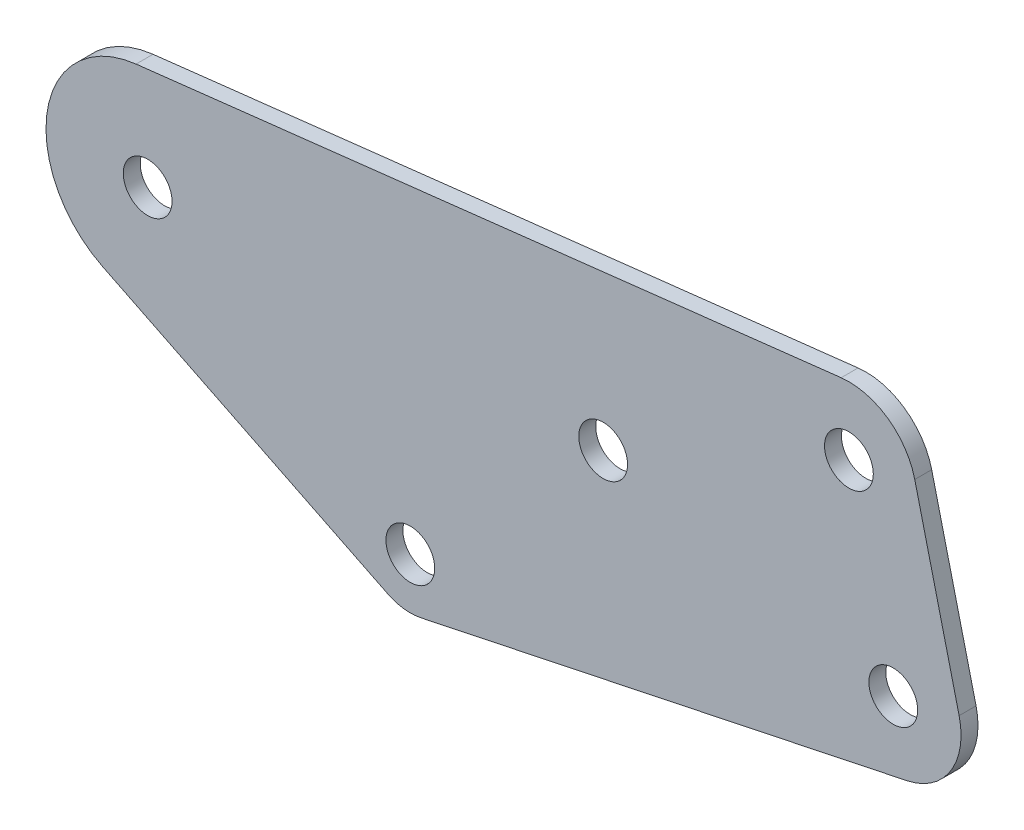
SolidWorks part; units mm, degrees
material "Delrin 2700 NC010, Low Viscosity Acetal Copolymer (SS)"
ref_plane "Front Plane" through (0, 0, 0) normal (0, 0, 1) x (1, 0, 0)
ref_plane "Top Plane" through (0, 0, 0) normal (0, 1, 0) x (1, 0, 0)
ref_plane "Right Plane" through (0, 0, 0) normal (1, 0, 0) x (0, 0, -1)
sketch "Sketch1" plane through (0, 0, 0) normal (0, 0, 1) x (1, 0, 0)
  line L0 (65.6922, 10.7345) -> (42.672, 0) construction
  line L1 (64.9683, 17.0431) -> (-1.0859, 9.4629)
  line L2 (-4.2174, -8.5404) -> (22.4975, -21.7327)
  line L5 (0, 0) -> (42.672, 0) construction
  line L6 (24.6063, -17.4625) -> (24.6062, 0) construction
  line L7 (0, 0) -> (47.7528, 0) construction
  line L8 (25.584, -22.1236) -> (71.1536, -12.5647)
  line L9 (76.0199, -4.8485) -> (71.8621, 12.236)
  circle A0 centre (0, 0) radius 2.286
  circle A1 centre (42.672, 0) radius 2.286
  circle A2 centre (65.6922, 10.7345) radius 2.286
  circle A3 centre (24.6063, -17.4625) radius 2.286
  arc A4 (-1.0859, 9.4629) -> (-4.2174, -8.5404) centre (0, 0) ccw
  arc A5 (22.4975, -21.7327) -> (25.584, -22.1236) centre (24.6063, -17.4625) ccw
  arc A7 (71.8621, 12.236) -> (64.9683, 17.0431) centre (65.6922, 10.7345) ccw
  circle A8 centre (69.85, -6.35) radius 2.286
  arc A9 (76.0199, -4.8485) -> (71.1536, -12.5647) centre (69.85, -6.35) cw
  dimension "D5" = 4.572
  dimension "D6" = 4.572
  dimension "D7" = 155
  dimension "D8" = 9.525
  dimension "D10" = 6.35
  dimension "D11" = 4.7625
  dimension "D15" = 6.35
  dimension "D1" = 42.672
  dimension "D2" = 25.4
  dimension "D3" = 17.4625
  dimension "D4" = 0
  dimension "D12" = 24.6062
  dimension "D13" = 6.35
  dimension "D14" = 69.85
extrude "Boss-Extrude1" add sketch "Sketch1" along normal blind 1.5875
